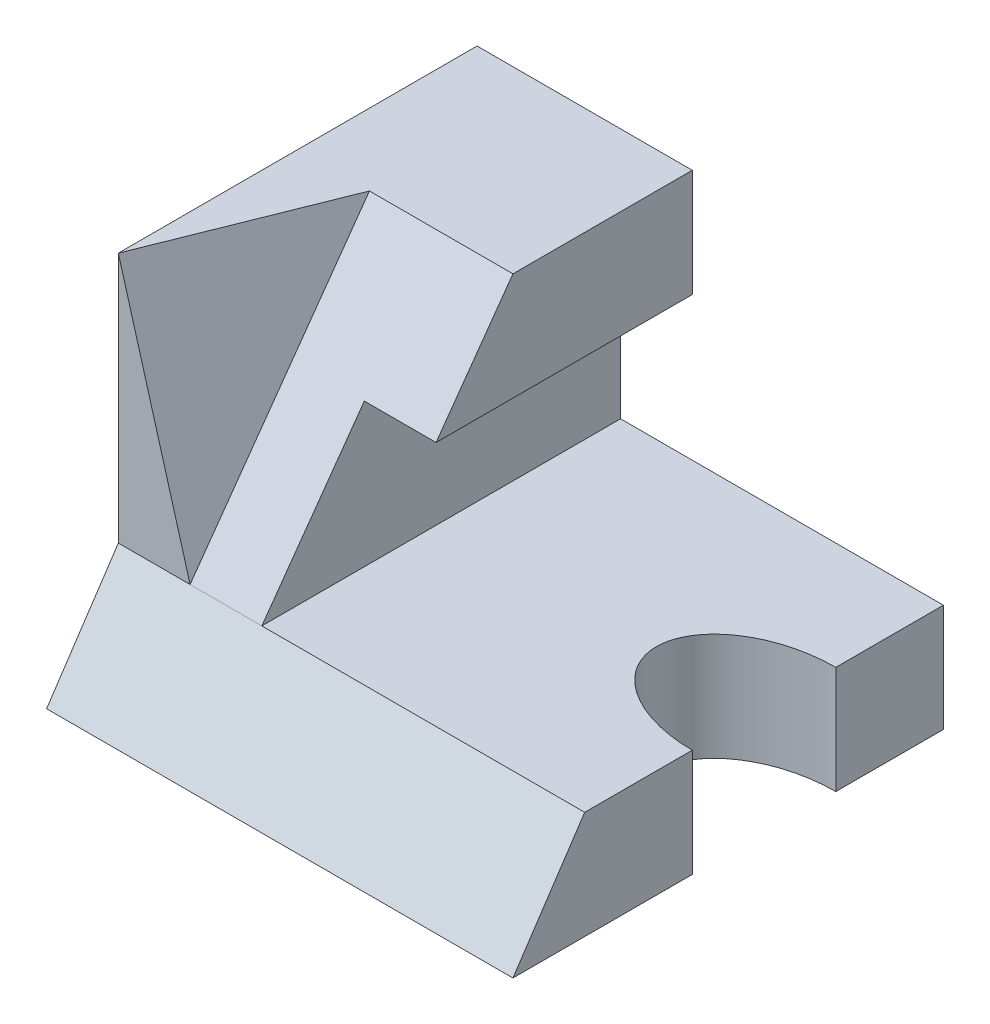
SolidWorks part; units mm, degrees
material "Copper"
ref_plane "Front Plane" through (0, 0, 0) normal (0, 0, 1) x (1, 0, 0)
ref_plane "Top Plane" through (0, 0, 0) normal (0, 1, 0) x (1, 0, 0)
ref_plane "Right Plane" through (0, 0, 0) normal (1, 0, 0) x (0, 0, -1)
sketch "Sketch1" plane through (0, 0, 0) normal (1, 0, 0) x (0, 0, -1)
  line L0 (0, 15) -> (0, 50)
  line L1 (0, 0) -> (-60, 0)
  line L2 (0, 0) -> (0, 15)
  line L3 (0, 15) -> (-50, 15)
  line L4 (-60, 0) -> (-50, 15)
  line L5 (0, 50) -> (-50, 50)
  line L6 (-50, 50) -> (-50, 15)
  line L7 (-50, 15) -> (-25, 50)
  line L8 (0, 35) -> (-35.7143, 35)
  point P9 (-33.6735, 35)
  dimension "D1" = 50
  dimension "D2" = 60
  dimension "D3" = 15
  dimension "D4" = 35
  dimension "D5" = 15
  dimension "D6" = 25
extrude "Boss-Extrude1" add sketch "Sketch1" along normal blind 65 contours L4 L1 L2 L3 region at (0, 7.2727, 27.5758)
extrude "Boss-Extrude2" add sketch "Sketch1<3>" along normal blind 20 contours L0 L8 L7 L3 region at (0, 24.4444, 21.627)
sketch "Sketch1<3>" plane through (0, 0, 0) normal (1, 0, 0) x (0, 0, -1) same geometry as "Sketch1"
extrude "Boss-Extrude3" add sketch "Sketch1<4>" along normal blind 30 contours L8 L0 L5 L7 region at (0, 42.0588, 15.3361)
sketch "Sketch1<4>" plane through (0, 0, 0) normal (1, 0, 0) x (0, 0, -1) same geometry as "Sketch1"
extrude "Boss-Extrude4" add sketch "Sketch1<5>" along normal blind 10 contours L6 L7 L5 region at (0, 38.3333, 41.6667)
sketch "Sketch1<5>" plane through (0, 0, 0) normal (1, 0, 0) x (0, 0, -1) same geometry as "Sketch1"
ref_plane "Plane1" through (27.6134, 7.8895, 11.0454) normal (-0.8974, -0.2564, -0.359) x (-0.3452, -0.0986, 0.9333)
sketch "Sketch2" plane through (27.6134, 7.8895, 11.0454) normal (-0.8974, -0.2564, -0.359) x (-0.3452, -0.0986, 0.9333)
  line L0 (41.7365, 48.0762) -> (14.9512, 45.329)
  line L1 (14.9512, 45.329) -> (41.7365, 11.6756)
  line L2 (41.7365, 11.6756) -> (41.7365, 48.0762)
extrude "Cut-Extrude1" cut sketch "Sketch2" along direction (-1, 0, 0) on the side against the normal blind 10
sketch "Sketch3" plane through (0, 15, 0) normal (0, 1, 0) x (1, 0, 0)
  line L0 (65, 0) -> (65, -50) construction
  ellipse E0 centre (65, -25) end of major axis (80, -25) minor radius 10
  point P1 (0, 0)
  point P7 (0, 0)
  dimension "D1" = 20
  dimension "D2" = 15
extrude "Cut-Extrude3" cut sketch "Sketch3" against normal up to next
